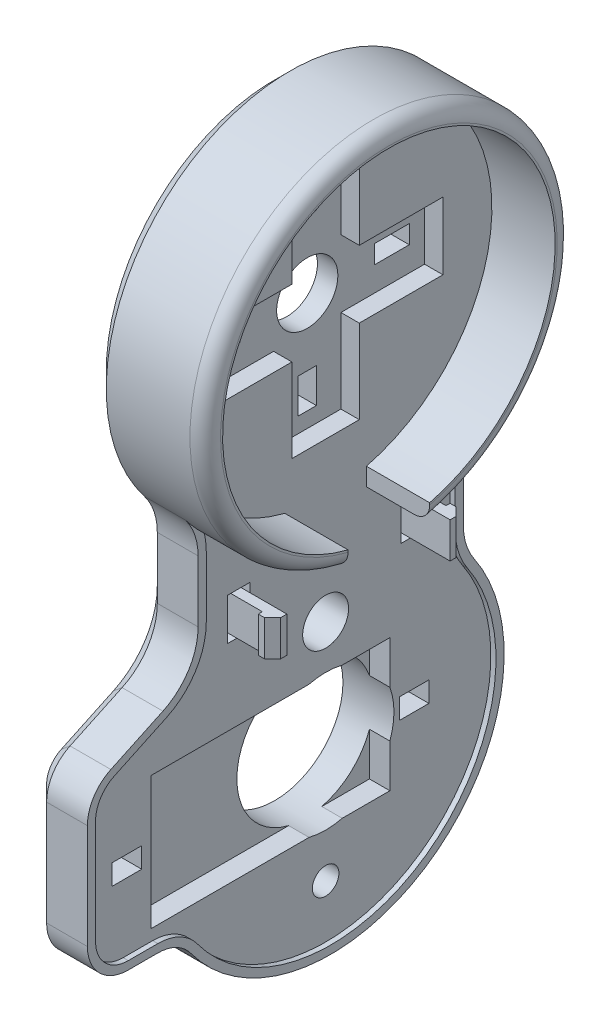
SolidWorks part; units mm, degrees
ref_plane "Front Plane" through (0, 0, 0) normal (0, 0, 1) x (1, 0, 0)
ref_plane "Top Plane" through (0, 0, 0) normal (0, 1, 0) x (1, 0, 0)
ref_plane "Right Plane" through (0, 0, 0) normal (1, 0, 0) x (0, 0, -1)
sketch "Sketch1" plane through (0, 0, 0) normal (1, 0, 0) x (0, 0, -1)
  line L0 (-53, 3.3371) -> (-53, -7.0385)
  line L1 (-82.9482, -28.4) -> (-85.85, -28.4)
  line L2 (-89.85, -24.4) -> (-89.85, -14.1397)
  line L3 (-87.5516, -10.5196) -> (-82.4476, -8.1205)
  line L4 (-79, -2.6905) -> (-79, 3.3371)
  arc A0 (-80.25, 7.0028) -> (-51.75, 7.0028) centre (-66, 18) cw
  arc A1 (-51.75, 7.0028) -> (-53, 3.3371) centre (-47, 3.3371) ccw
  arc A2 (-53, -7.0385) -> (-51.9565, -10.4198) centre (-47, -7.0385) ccw
  arc A3 (-51.9565, -10.4198) -> (-79.7199, -30.0381) centre (-66, -20) cw
  arc A4 (-79.7199, -30.0381) -> (-82.9482, -28.4) centre (-82.9482, -32.4) ccw
  arc A5 (-85.85, -28.4) -> (-89.85, -24.4) centre (-85.85, -24.4) cw
  arc A6 (-89.85, -14.1397) -> (-87.5516, -10.5196) centre (-85.85, -14.1397) cw
  arc A7 (-82.4476, -8.1205) -> (-79, -2.6905) centre (-85, -2.6905) ccw
  arc A8 (-79, 3.3371) -> (-80.25, 7.0028) centre (-85, 3.3371) ccw
extrude "Boss-Extrude1" add sketch "Sketch1" along normal blind 5.5 from offset 60.6 offset against normal yes
sketch "Sketch2" plane through (0, 0, 0) normal (1, 0, 0) x (0, 0, -1)
  line L0 (-53.8, 3.3371) -> (-53.8, -7.0385)
  line L1 (-82.9482, -27.6) -> (-85.85, -27.6)
  line L2 (-89.05, -24.4) -> (-89.05, -14.1397)
  line L3 (-87.2113, -11.2436) -> (-82.1073, -8.8446)
  line L4 (-78.2, -2.6905) -> (-78.2, 3.3371)
  arc A0 (-79.6167, 7.4916) -> (-52.3833, 7.4916) centre (-66, 18) cw
  arc A1 (-52.3833, 7.4916) -> (-53.8, 3.3371) centre (-47, 3.3371) ccw
  arc A2 (-53.8, -7.0385) -> (-52.6174, -10.8706) centre (-47, -7.0385) ccw
  arc A3 (-52.6174, -10.8706) -> (-79.0743, -29.5657) centre (-66, -20) cw
  arc A4 (-79.0743, -29.5657) -> (-82.9482, -27.6) centre (-82.9482, -32.4) ccw
  arc A5 (-85.85, -27.6) -> (-89.05, -24.4) centre (-85.85, -24.4) cw
  arc A6 (-89.05, -14.1397) -> (-87.2113, -11.2436) centre (-85.85, -14.1397) cw
  arc A7 (-82.1073, -8.8446) -> (-78.2, -2.6905) centre (-85, -2.6905) ccw
  arc A8 (-78.2, 3.3371) -> (-79.6167, 7.4916) centre (-85, 3.3371) ccw
extrude "Boss-Extrude2" add sketch "Sketch2" along normal blind 0.6 from offset 55.6 separate body offset against normal yes
combine bodies "Combine1" operation type subtract main body 101 bodies to subtract 102
sketch "Sketch3" plane through (0, 0, 0) normal (1, 0, 0) x (0, 0, -1)
  circle A0 centre (-66, 18) radius 18
  circle A1 centre (-66, 18) radius 16.3
extrude "Boss-Extrude3" add sketch "Sketch3" along normal blind 6.2 from offset 55.6 offset against normal yes
chamfer "Chamfer1" distance 1.5 angle 45 14 edges at (-60.6, -5.9065, 79.9347) (-60.6, -9.3201, 84.9996) (-60.6, 0.3233, 79) (-60.6, -11.9956, 89.2269) (-60.6, 5.2736, 79.3211) (-60.6, -19.2698, 89.85) (-60.6, 36, 66) (-60.6, -27.2284, 88.6784) (-60.6, 5.2736, 52.6789) (-60.6, -28.4, 84.3991) (-60.6, -1.8507, 53) (-60.6, -28.833, 81.1381) (-60.6, -8.8078, 52.7332) (-60.6, -33.8836, 56.1895)
fillet "Fillet1" radius 1.5 1 edges at (-49.4, 18, 48)
sketch "Sketch4" plane through (0, 0, 0) normal (0, 0, 1) x (1, 0, 0)
  line L1 (-57.4, 6.5) -> (-55.1, 6.5)
  line L2 (-57.4, 6.5) -> (-57.4, 29.5)
  line L3 (-57.4, 29.5) -> (-55.1, 29.5)
  line L4 (-55.1, 6.5) -> (-55.1, 29.5)
extrude "Boss-Extrude4" add sketch "Sketch4" along normal blind 6.6 from offset 62.7 separate body
combine bodies "Combine2" operation type subtract main body 104 bodies to subtract 105
sketch "Sketch5" plane through (0, 0, 0) normal (0, 0, 1) x (1, 0, 0)
  line L1 (-57.4, 14.7) -> (-55.1, 14.7)
  line L2 (-57.4, 14.7) -> (-57.4, 21.3)
  line L3 (-57.4, 21.3) -> (-55.1, 21.3)
  line L4 (-55.1, 14.7) -> (-55.1, 21.3)
extrude "Boss-Extrude5" add sketch "Sketch5" along normal blind 23 from offset 54.5 separate body
combine bodies "Combine3" operation type subtract main body 106 bodies to subtract 107
sketch "Sketch6" plane through (0, 0, 0) normal (1, 0, 0) x (0, 0, -1)
  circle A0 centre (-66, 18) radius 4.6
extrude "Boss-Extrude6" add sketch "Sketch6" along normal blind 2.3 from offset 57.4 separate body offset against normal yes
combine bodies "Combine4" operation type subtract main body 108 bodies to subtract 109
sketch "Sketch7" plane through (0, 0, 0) normal (1, 0, 0) x (0, 0, -1)
  circle A0 centre (-66, 18) radius 6.1
extrude "Boss-Extrude7" add sketch "Sketch7" along normal blind 1.7 from offset 61.1 separate body offset against normal yes
combine bodies "Combine5" operation type subtract main body 110 bodies to subtract 111
sketch "Sketch8" plane through (0, 0, 0) normal (1, 0, 0) x (0, 0, -1)
  circle A0 centre (-66, 18) radius 3
extrude "Boss-Extrude8" add sketch "Sketch8" along normal blind 2.2 from offset 59.5 separate body offset against normal yes
combine bodies "Combine6" operation type subtract main body 112 bodies to subtract 113
sketch "Sketch9" plane through (0, 0, 0) normal (0, 0, 1) x (1, 0, 0)
  line L1 (-59.6, 24.6) -> (-57.3, 24.6)
  line L2 (-59.6, 24.6) -> (-59.6, 28)
  line L3 (-59.6, 28) -> (-57.3, 28)
  line L4 (-57.3, 24.6) -> (-57.3, 28)
extrude "Boss-Extrude9" add sketch "Sketch9" along normal blind 1.8 from offset 65.1 separate body
combine bodies "Combine7" operation type subtract main body 114 bodies to subtract 115
sketch "Sketch10" plane through (0, 0, 0) normal (0, 0, 1) x (1, 0, 0)
  line L1 (-59.6, 17.1) -> (-57.3, 17.1)
  line L2 (-59.6, 17.1) -> (-59.6, 18.9)
  line L3 (-59.6, 18.9) -> (-57.3, 18.9)
  line L4 (-57.3, 17.1) -> (-57.3, 18.9)
extrude "Boss-Extrude10" add sketch "Sketch10" along normal blind 3.4 from offset 72.6 separate body
combine bodies "Combine8" operation type subtract main body 116 bodies to subtract 117
sketch "Sketch11" plane through (0, 0, 0) normal (0, 0, 1) x (1, 0, 0)
  line L1 (-59.6, 8) -> (-57.3, 8)
  line L2 (-59.6, 8) -> (-59.6, 11.4)
  line L3 (-59.6, 11.4) -> (-57.3, 11.4)
  line L4 (-57.3, 8) -> (-57.3, 11.4)
extrude "Boss-Extrude11" add sketch "Sketch11" along normal blind 1.8 from offset 65.1 separate body
combine bodies "Combine9" operation type subtract main body 118 bodies to subtract 119
sketch "Sketch12" plane through (0, 0, 0) normal (0, 0, 1) x (1, 0, 0)
  line L1 (-59.6, 17.1) -> (-57.3, 17.1)
  line L2 (-59.6, 17.1) -> (-59.6, 18.9)
  line L3 (-59.6, 18.9) -> (-57.3, 18.9)
  line L4 (-57.3, 17.1) -> (-57.3, 18.9)
extrude "Boss-Extrude12" add sketch "Sketch12" along normal blind 3.4 from offset 56 separate body
combine bodies "Combine10" operation type subtract main body 120 bodies to subtract 121
sketch "Sketch13" plane through (0, 0, 0) normal (0, 0, 1) x (1, 0, 0)
  line L1 (-55.6, -0.6) -> (-49.3, -0.6)
  line L2 (-55.6, -0.6) -> (-55.6, 2.4984)
  line L3 (-55.6, 2.4984) -> (-49.3, 2.4984)
  line L4 (-49.3, -0.6) -> (-49.3, 2.4984)
extrude "Boss-Extrude13" add sketch "Sketch13" along normal blind 8 from offset 62 separate body
combine bodies "Combine11" operation type subtract main body 122 bodies to subtract 123
sketch "Sketch14" plane through (0, 0, 0) normal (0, 0, 1) x (1, 0, 0)
  line L1 (-59.6, -21) -> (-55.5, -21)
  line L2 (-59.6, -21) -> (-59.6, -19)
  line L3 (-59.6, -19) -> (-55.5, -19)
  line L4 (-55.5, -21) -> (-55.5, -19)
extrude "Boss-Extrude14" add sketch "Sketch14" along normal blind 2.9 from offset 55.875 separate body
combine bodies "Combine12" operation type subtract main body 124 bodies to subtract 125
sketch "Sketch15" plane through (0, 0, 0) normal (0, 0, 1) x (1, 0, 0)
  line L1 (-59.6, -21) -> (-55.5, -21)
  line L2 (-59.6, -21) -> (-59.6, -19)
  line L3 (-59.6, -19) -> (-55.5, -19)
  line L4 (-55.5, -21) -> (-55.5, -19)
extrude "Boss-Extrude15" add sketch "Sketch15" along normal blind 2.9 from offset 84.025 separate body
combine bodies "Combine13" operation type subtract main body 126 bodies to subtract 127
sketch "Sketch16" plane through (0, 0, 0) normal (0, 0, 1) x (1, 0, 0)
  line L1 (-57.6, -26.5) -> (-55.5, -26.5)
  line L2 (-57.6, -26.5) -> (-57.6, -13.5)
  line L3 (-57.6, -13.5) -> (-55.5, -13.5)
  line L4 (-55.5, -26.5) -> (-55.5, -13.5)
extrude "Boss-Extrude16" add sketch "Sketch16" along normal blind 23.4 from offset 59.7 separate body
combine bodies "Combine14" operation type subtract main body 128 bodies to subtract 129
sketch "Sketch17" plane through (0, 0, 0) normal (1, 0, 0) x (0, 0, -1)
  circle A0 centre (-66, -20) radius 6.7
extrude "Boss-Extrude17" add sketch "Sketch17" along normal blind 5.6 from offset 61.1 separate body offset against normal yes
combine bodies "Combine15" operation type subtract main body 130 bodies to subtract 131
sketch "Sketch18" plane through (0, 0, 0) normal (1, 0, 0) x (0, 0, -1)
  circle A0 centre (-66, -9) radius 2.25
extrude "Boss-Extrude18" add sketch "Sketch18" along normal blind 5.6 from offset 61.1 separate body offset against normal yes
combine bodies "Combine16" operation type subtract main body 132 bodies to subtract 133
sketch "Sketch19" plane through (0, 0, 0) normal (1, 0, 0) x (0, 0, -1)
  circle A0 centre (-66, -31) radius 2.3
extrude "Boss-Extrude19" add sketch "Sketch19" along normal blind 1.9 from offset 61.1 separate body offset against normal yes
combine bodies "Combine17" operation type subtract main body 134 bodies to subtract 135
sketch "Sketch20" plane through (0, 0, 0) normal (1, 0, 0) x (0, 0, -1)
  circle A0 centre (-66, -31) radius 1.3
extrude "Boss-Extrude20" add sketch "Sketch20" along normal blind 3.75 from offset 59.25 separate body offset against normal yes
combine bodies "Combine18" operation type subtract main body 136 bodies to subtract 137
sketch "Sketch21" plane through (0, 0, 0) normal (0, 0, 1) x (1, 0, 0)
  line L1 (-58.6, -6.05) -> (-55.5, -6.05)
  line L2 (-58.6, -6.05) -> (-58.6, -1.95)
  line L3 (-58.6, -1.95) -> (-55.5, -1.95)
  line L4 (-55.5, -6.05) -> (-55.5, -1.95)
extrude "Boss-Extrude21" add sketch "Sketch21" along normal blind 2.2 from offset 56.4 separate body
combine bodies "Combine19" operation type subtract main body 138 bodies to subtract 139
sketch "Sketch22" plane through (0, 0, 0) normal (0, 1, 0) x (1, 0, 0)
  line L0 (-58.8, -58) -> (-58.8, -57)
  line L1 (-58.8, -57) -> (-52.8, -57)
  line L2 (-52.8, -57) -> (-52.8, -56.6)
  line L3 (-52.8, -56.6) -> (-52.2, -56.6)
  line L4 (-52.2, -56.6) -> (-51.4, -57.4)
  line L5 (-51.4, -57.4) -> (-51.4, -58)
  line L6 (-51.4, -58) -> (-58.8, -58)
extrude "Boss-Extrude22" add sketch "Sketch22" along normal blind 3.5 from offset 5.75 offset against normal yes
sketch "Sketch23" plane through (0, 0, 0) normal (0, 0, 1) x (1, 0, 0)
  line L1 (-58.6, -6.05) -> (-55.5, -6.05)
  line L2 (-58.6, -6.05) -> (-58.6, -1.95)
  line L3 (-58.6, -1.95) -> (-55.5, -1.95)
  line L4 (-55.5, -6.05) -> (-55.5, -1.95)
extrude "Boss-Extrude23" add sketch "Sketch23" along normal blind 2.2 from offset 73.4 separate body
combine bodies "Combine20" operation type subtract main body 141 bodies to subtract 142
sketch "Sketch24" plane through (0, 0, 0) normal (0, 1, 0) x (1, 0, 0)
  line L0 (-58.8, -74) -> (-58.8, -75)
  line L1 (-58.8, -75) -> (-52.8, -75)
  line L2 (-52.8, -75) -> (-52.8, -75.4)
  line L3 (-52.8, -75.4) -> (-52.2, -75.4)
  line L4 (-52.2, -75.4) -> (-51.4, -74.6)
  line L5 (-51.4, -74.6) -> (-51.4, -74)
  line L6 (-51.4, -74) -> (-58.8, -74)
extrude "Boss-Extrude24" add sketch "Sketch24" along normal blind 3.5 from offset 5.75 offset against normal yes
